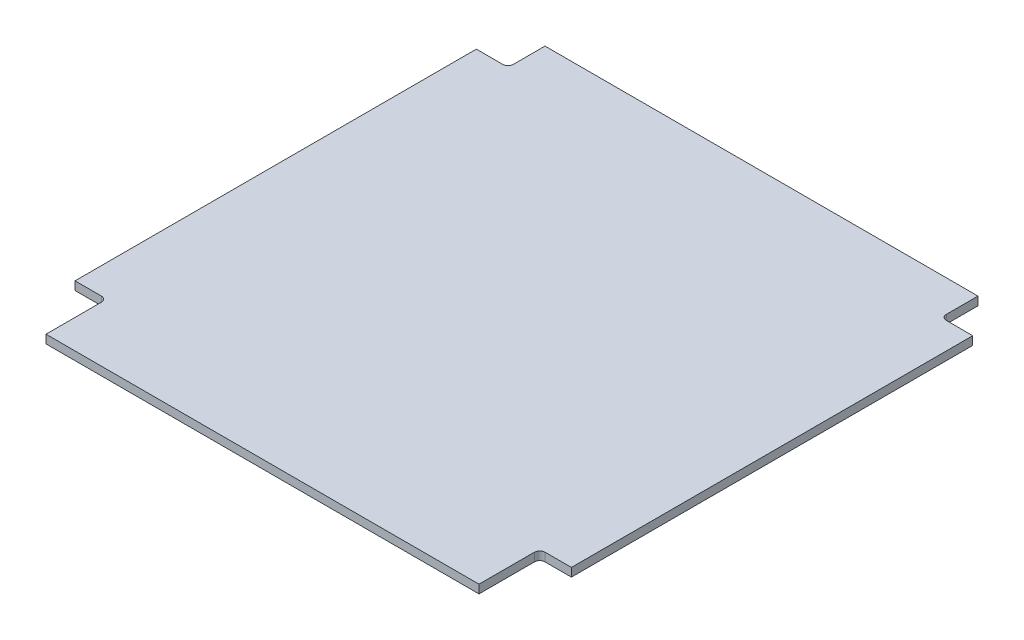
SolidWorks part; units mm, degrees
ref_plane "Front Plane" through (0, 0, 0) normal (0, 0, 1) x (1, 0, 0)
ref_plane "Top Plane" through (0, 0, 0) normal (0, 1, 0) x (1, 0, 0)
ref_plane "Right Plane" through (0, 0, 0) normal (1, 0, 0) x (0, 0, -1)
sketch "Sketch1" plane through (0, 0, 0) normal (0, 1, 0) x (1, 0, 0)
  line L5 (-41, -38) -> (41, 38) construction
  line L6 (-41, 38) -> (41, -38) construction
  line L8 (-41, 38) -> (-41, 45)
  line L9 (-41, 45) -> (41, 45)
  line L10 (41, 38) -> (41, 45)
  line L12 (-41, -38) -> (-41, -49.5)
  line L13 (-41, -49.5) -> (41, -49.5)
  line L14 (41, -38) -> (41, -49.5)
  line L15 (-41, 38) -> (-47, 38)
  line L17 (-41, -38) -> (-47, -38)
  line L18 (-47, 38) -> (-47, -38)
  line L19 (41, 38) -> (47, 38)
  line L21 (41, -38) -> (47, -38)
  line L22 (47, 38) -> (47, -38)
  point P0 (0, 0)
  dimension "D1" = 82
  dimension "D2" = 76
  dimension "D3" = 6
  dimension "D4" = 11.5
  dimension "D5" = 7
  dimension "D6" = 6
extrude "Boss-Extrude1" add sketch "Sketch1" along normal blind 1.6
sketch "Sketch2" plane through (0, 1.6, 0) normal (0, 1, 0) x (1, 0, 0)
  circle A0 centre (0, 0) radius 15
  dimension "D1" = 30
extrude "Cut-Extrude1" [suppressed] cut sketch "Sketch2" against normal up to next
fillet "Fillet1" radius 1 4 edges at (-41, 0.8, 38) (-41, 0.8, -38) (41, 0.8, -38) (41, 0.8, 38)
